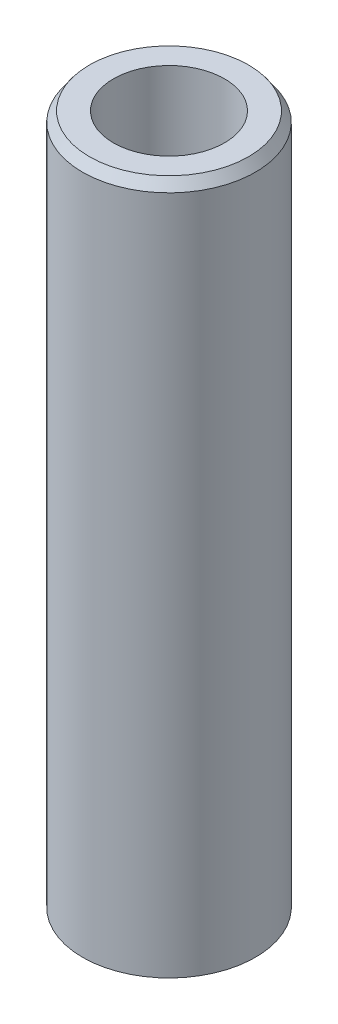
SolidWorks part; units mm, degrees
ref_plane "Front Plane" through (0, 0, 0) normal (0, 0, 1) x (1, 0, 0)
ref_plane "Top Plane" through (0, 0, 0) normal (0, 1, 0) x (1, 0, 0)
ref_plane "Right Plane" through (0, 0, 0) normal (1, 0, 0) x (0, 0, -1)
sketch "Sketch1" plane through (0, 0, 0) normal (0, 1, 0) x (1, 0, 0)
  circle A0 centre (0, 0) radius 25
  dimension "SHAFT_OD" = 50
extrude "Boss-Extrude1" add sketch "Sketch1" along normal blind 201.4147
sketch "Sketch2" plane through (0, 0, 0) normal (0, 1, 0) x (1, 0, 0)
  circle A0 centre (0, 0) radius 16.055
  dimension "BORE_D" = 32.1101
extrude "Cut-Extrude1" cut sketch "Sketch2" along normal through all
chamfer "Chamfer1" distance 2.8608 angle 35.057 2 edges at (0, 201.4147, 25) (0, 0, 25) first distance on face at (0, 201.4147, 25) first distance on face at (0, 0, 16.055)
